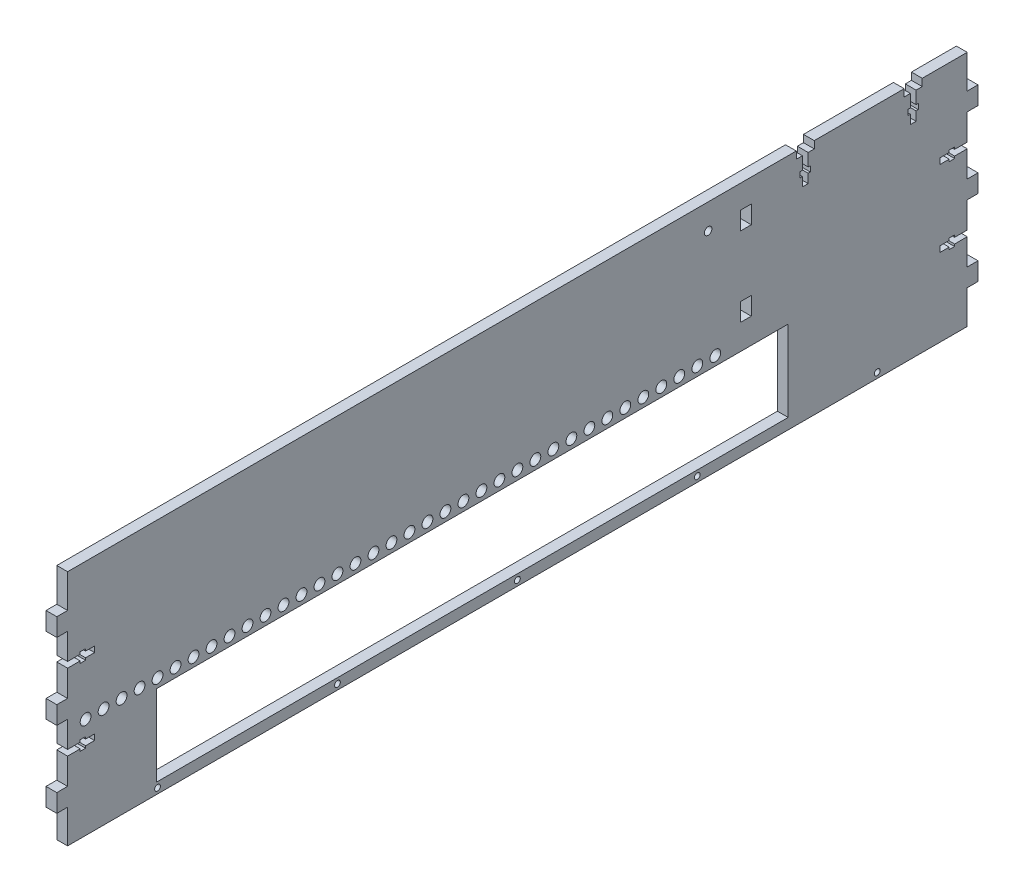
SolidWorks part; units mm, degrees
ref_plane "Front Plane" through (0, 0, 0) normal (0, 0, 1) x (1, 0, 0)
ref_plane "Top Plane" through (0, 0, 0) normal (0, 1, 0) x (1, 0, 0)
ref_plane "Right Plane" through (0, 0, 0) normal (1, 0, 0) x (0, 0, -1)
sketch "Sketch1" plane through (0, 0, 0) normal (1, 0, 0) x (0, 0, -1)
  line L1 (-250, -66) -> (250, -66)
  line L2 (-250, -66) -> (-250, 66)
  line L3 (-250, 66) -> (250, 66)
  line L4 (250, -66) -> (250, 66)
  line L5 (-250, -66) -> (250, 66) construction
  line L6 (-250, 66) -> (250, -66) construction
  point P0 (0, 0)
  dimension "D1" = 132
  dimension "D2" = 500
extrude "Boss-Extrude1" add sketch "Sketch1" along normal blind 6
sketch "Sketch4" plane through (0, 0, 250) normal (0, 0, 1) x (1, 0, 0)
  line L0 (0, 66) -> (0, -66) construction
  line L1 (0, 47.3321) -> (6, 47.3321)
  line L2 (0, 47.3321) -> (0, 37.3321)
  line L3 (0, 37.3321) -> (6, 37.3321)
  line L4 (6, 47.3321) -> (6, 37.3321)
  line L5 (6, 66) -> (6, -66) construction
  line L6 (0, 37.3321) -> (6, 37.3321) construction
  line L7 (0, -66) -> (0, 66) construction
  line L8 (6, 47.3321) -> (0, 47.3321) construction
  line L9 (0, -5) -> (6, -5) construction
  line L10 (0, -5) -> (6, -5)
  line L11 (0, -5) -> (0, 5)
  line L12 (0, 5) -> (6, 5)
  line L13 (6, -5) -> (6, 5)
  line L14 (6, -66) -> (6, 66) construction
  line L15 (6, 5) -> (0, 5) construction
  line L16 (6, -37.3321) -> (0, -37.3321) construction
  line L17 (0, -47.3321) -> (6, -47.3321)
  line L18 (0, -47.3321) -> (0, -37.3321)
  line L19 (0, -37.3321) -> (6, -37.3321)
  line L20 (6, -47.3321) -> (6, -37.3321)
  line L21 (0, -47.3321) -> (6, -47.3321) construction
extrude "Boss-Extrude2" add sketch "Sketch4" along normal blind 6
sketch "Sketch5" plane through (0, 0, 0) normal (-1, 0, 0) x (0, 0, 1)
  line L0 (250, 37.3321) -> (250, 5) construction
  line L1 (250, 5) -> (250, -5) construction
  line L2 (250, -5) -> (250, -37.3321) construction
  line L3 (250, 21.1661) -> (235, 21.1661) construction
  line L4 (240, -23.9661) -> (243, -18.3661) construction
  line L5 (250, 22.7661) -> (235, 22.7661)
  line L6 (240, -18.3661) -> (243, -23.9661) construction
  line L7 (250, 19.5661) -> (235, 19.5661)
  line L8 (250, -21.1661) -> (235, -21.1661) construction
  line L9 (250, 22.7661) -> (250, 19.5661)
  line L10 (235, 22.7661) -> (235, 19.5661)
  line L11 (243, -18.3661) -> (243, -23.9661)
  line L12 (240, -23.9661) -> (243, -23.9661)
  line L13 (250, 0) -> (222.8268, 0) construction
  line L14 (240, 18.3661) -> (243, 18.3661)
  line L15 (240, 18.3661) -> (240, 23.9661)
  line L16 (240, 23.9661) -> (243, 23.9661)
  line L17 (243, 18.3661) -> (243, 23.9661)
  line L18 (240, 18.3661) -> (243, 23.9661) construction
  line L19 (240, 23.9661) -> (243, 18.3661) construction
  line L20 (240, -18.3661) -> (240, -23.9661)
  line L21 (240, -18.3661) -> (243, -18.3661)
  line L22 (235, -22.7661) -> (235, -19.5661)
  line L23 (250, -22.7661) -> (250, -19.5661)
  line L24 (250, -19.5661) -> (235, -19.5661)
  line L25 (250, -22.7661) -> (235, -22.7661)
  point P20 (241.5, 21.1661)
  point P29 (241.5, -21.1661)
  dimension "D3" = 15
  dimension "D4" = 7
  dimension "D5" = 3
  dimension "D6" = 5.6
  dimension "D1" = 1.6
  dimension "D2" = 1.6
extrude "Cut-Extrude3" cut sketch "Sketch5" against normal up to next contours L17 L7 L9 L5 | L7 L17 L5 L15 | L5 L17 L16 L15 | L14 L17 L7 L15 | L7 L15 L5 L10 | L25 L23 L24 L11 | L25 L11 L24 L20 | L24 L11 L21 L20 | L11 L25 L20 L12 | L25 L20 L24 L22 region at (0, 21.1661, 246.5) region at (0, 21.1661, 241.5) region at (0, 23.3661, 241.5) region at (0, 21.1661, 237.5) region at (0, 18.9661, 241.5) region at (0, -18.9661, 241.5) region at (0, -21.1661, 246.5) region at (0, -21.1661, 241.5) region at (0, -23.3661, 241.5) region at (0, -21.1661, 237.5)
sketch "Sketch6" plane through (0, 0, -250) normal (0, 0, -1) x (-1, 0, 0)
  line L0 (0, 47.3321) -> (0, 37.3321) construction
  line L1 (0, 37.3321) -> (-6, 37.3321) construction
  line L2 (-6, 37.3321) -> (-6, 47.3321) construction
  line L3 (-6, 47.3321) -> (0, 47.3321) construction
  line L4 (0, 5) -> (0, -5) construction
  line L5 (0, -5) -> (-6, -5) construction
  line L6 (-6, -5) -> (-6, 5) construction
  line L7 (-6, 5) -> (0, 5) construction
  line L8 (0, -37.3321) -> (0, -47.3321) construction
  line L9 (0, -47.3321) -> (-6, -47.3321) construction
  line L10 (-6, -47.3321) -> (-6, -37.3321) construction
  line L11 (-6, -37.3321) -> (0, -37.3321) construction
  line L12 (0, 47.3321) -> (0, 37.3321)
  line L13 (0, 37.3321) -> (-6, 37.3321)
  line L14 (-6, 37.3321) -> (-6, 47.3321)
  line L15 (-6, 47.3321) -> (0, 47.3321)
  line L16 (0, 5) -> (0, -5)
  line L17 (0, -5) -> (-6, -5)
  line L18 (-6, -5) -> (-6, 5)
  line L19 (-6, 5) -> (0, 5)
  line L20 (0, -37.3321) -> (0, -47.3321)
  line L21 (0, -47.3321) -> (-6, -47.3321)
  line L22 (-6, -47.3321) -> (-6, -37.3321)
  line L23 (-6, -37.3321) -> (0, -37.3321)
extrude "Boss-Extrude3" add sketch "Sketch6" along normal blind 6
sketch "Sketch7" plane through (0, 0, 0) normal (-1, 0, 0) x (0, 0, 1)
  line L0 (0, 0) -> (0, -63.2146) construction
  line L1 (240, 22.7661) -> (240, 23.9661) construction
  line L2 (240, 22.7661) -> (235, 22.7661) construction
  line L3 (235, 22.7661) -> (235, 19.5661) construction
  line L4 (240, 19.5661) -> (235, 19.5661) construction
  line L5 (240, 18.3661) -> (240, 19.5661) construction
  line L6 (240, 18.3661) -> (243, 18.3661) construction
  line L7 (243, 18.3661) -> (243, 19.5661) construction
  line L8 (250, 19.5661) -> (243, 19.5661) construction
  line L9 (250, 22.7661) -> (243, 22.7661) construction
  line L10 (240, 23.9661) -> (243, 23.9661) construction
  line L11 (243, 22.7661) -> (243, 23.9661) construction
  line L12 (240, 22.7661) -> (235, 22.7661) construction
  line L13 (235, 22.7661) -> (235, 19.5661) construction
  line L14 (240, 19.5661) -> (235, 19.5661) construction
  line L15 (240, 18.3661) -> (240, 19.5661) construction
  line L16 (240, 18.3661) -> (243, 18.3661) construction
  line L17 (243, 18.3661) -> (243, 19.5661) construction
  line L18 (250, 19.5661) -> (243, 19.5661) construction
  line L19 (250, 22.7661) -> (243, 22.7661) construction
  line L20 (240, 23.9661) -> (243, 23.9661) construction
  line L21 (243, 22.7661) -> (243, 23.9661) construction
  line L22 (240, 22.7661) -> (240, 23.9661) construction
  line L23 (250, -19.5661) -> (243, -19.5661) construction
  line L24 (240, -18.3661) -> (243, -18.3661) construction
  line L25 (243, -18.3661) -> (243, -19.5661) construction
  line L26 (240, -18.3661) -> (240, -19.5661) construction
  line L27 (240, -19.5661) -> (235, -19.5661) construction
  line L28 (235, -22.7661) -> (235, -19.5661) construction
  line L29 (240, -22.7661) -> (235, -22.7661) construction
  line L30 (240, -22.7661) -> (240, -23.9661) construction
  line L31 (240, -23.9661) -> (243, -23.9661) construction
  line L32 (243, -22.7661) -> (243, -23.9661) construction
  line L33 (250, -22.7661) -> (243, -22.7661) construction
  line L34 (250, -19.5661) -> (243, -19.5661) construction
  line L35 (240, -18.3661) -> (243, -18.3661) construction
  line L36 (243, -18.3661) -> (243, -19.5661) construction
  line L37 (240, -18.3661) -> (240, -19.5661) construction
  line L38 (240, -19.5661) -> (235, -19.5661) construction
  line L39 (235, -22.7661) -> (235, -19.5661) construction
  line L40 (240, -22.7661) -> (235, -22.7661) construction
  line L41 (240, -22.7661) -> (240, -23.9661) construction
  line L42 (240, -23.9661) -> (243, -23.9661) construction
  line L43 (243, -22.7661) -> (243, -23.9661) construction
  line L44 (250, -22.7661) -> (243, -22.7661) construction
  line L45 (250, 22.7661) -> (250, 19.5661) construction
  line L46 (250, -19.5661) -> (250, -22.7661) construction
  line L47 (-250, -19.5661) -> (-250, -22.7661)
  line L48 (-250, 22.7661) -> (-250, 19.5661)
  line L49 (-250, -22.7661) -> (-243, -22.7661)
  line L50 (-243, -22.7661) -> (-243, -23.9661)
  line L51 (-240, -23.9661) -> (-243, -23.9661)
  line L52 (-240, -22.7661) -> (-240, -23.9661)
  line L53 (-240, -22.7661) -> (-235, -22.7661)
  line L54 (-235, -22.7661) -> (-235, -19.5661)
  line L55 (-240, -19.5661) -> (-235, -19.5661)
  line L56 (-240, -18.3661) -> (-240, -19.5661)
  line L57 (-243, -18.3661) -> (-243, -19.5661)
  line L58 (-240, -18.3661) -> (-243, -18.3661)
  line L59 (-250, -19.5661) -> (-243, -19.5661)
  line L60 (-240, 22.7661) -> (-240, 23.9661)
  line L61 (-243, 22.7661) -> (-243, 23.9661)
  line L62 (-240, 23.9661) -> (-243, 23.9661)
  line L63 (-250, 22.7661) -> (-243, 22.7661)
  line L64 (-250, 19.5661) -> (-243, 19.5661)
  line L65 (-243, 18.3661) -> (-243, 19.5661)
  line L66 (-240, 18.3661) -> (-243, 18.3661)
  line L67 (-240, 18.3661) -> (-240, 19.5661)
  line L68 (-240, 19.5661) -> (-235, 19.5661)
  line L69 (-235, 22.7661) -> (-235, 19.5661)
  line L70 (-240, 22.7661) -> (-235, 22.7661)
extrude "Cut-Extrude4" cut sketch "Sketch7" against normal up to next
sketch "Sketch8" plane through (0, 0, 0) normal (-1, 0, 0) x (0, 0, 1)
  line L0 (200, -15.55) -> (-150, -15.55) construction
  line L1 (200, -15.55) -> (-150, -15.55) construction
  line L2 (200, -15.55) -> (200, -60) construction
  line L3 (200, -15.55) -> (200, -60) construction
  line L186 (-150, -15.55) -> (-150, -60) construction
  line L187 (-150, -60) -> (200, -60) construction
  line L188 (200.5, -15.05) -> (200.5, -60)
  line L189 (200.5, -15.05) -> (-150.5, -15.05)
  line L190 (-150.5, -15.05) -> (-150.5, -60)
  line L191 (-150.5, -60) -> (200.5, -60)
  dimension "D1" = 0.5
extrude "Cut-Extrude5" cut sketch "Sketch8" against normal up to next
sketch "Sketch10" plane through (6, 0, 0) normal (1, 0, 0) x (0, 0, -1)
  line L0 (0, 0) -> (0, -66) construction
  line L1 (-250, -66) -> (250, -66) construction
  line L2 (0, -63) -> (250, -63) construction
  line L3 (250, -66) -> (250, -47.3321) construction
  circle A0 centre (0, -63) radius 1.6
  circle A1 centre (100, -63) radius 1.6
  circle A2 centre (200, -63) radius 1.6
  circle A3 centre (-100, -63) radius 1.6
  circle A4 centre (-200, -63) radius 1.6
  dimension "D2" = 3.2
  dimension "D1" = 3
  dimension "D3" = 100
  dimension "D4" = 100
extrude "Cut-Extrude7" cut sketch "Sketch10" against normal up to next
sketch "Sketch11" plane through (6, 0, 0) normal (1, 0, 0) x (0, 0, -1)
  line L0 (130, 43) -> (130, 53) construction
  line L1 (130, 53) -> (124, 53) construction
  line L2 (124, 53) -> (124, 43) construction
  line L3 (124, 43) -> (130, 43) construction
  line L4 (130, -1) -> (130, 9) construction
  line L5 (130, 9) -> (124, 9) construction
  line L6 (124, 9) -> (124, -1) construction
  line L7 (124, -1) -> (130, -1) construction
  line L8 (130, 43) -> (130, 53)
  line L9 (130, 53) -> (124, 53)
  line L10 (124, 53) -> (124, 43)
  line L11 (124, 43) -> (130, 43)
  line L12 (130, -1) -> (130, 9)
  line L13 (130, 9) -> (124, 9)
  line L14 (124, 9) -> (124, -1)
  line L15 (124, -1) -> (130, -1)
extrude "Cut-Extrude8" cut sketch "Sketch11" against normal up to next
sketch "Sketch12" plane through (0, 0, 0) normal (-1, 0, 0) x (0, 0, 1)
  line L0 (-124, 53) -> (-124, 43) construction
  line L1 (-250, 66) -> (250, 66) construction
  circle A0 centre (-106, 52) radius 2.1
  dimension "D1" = 18
  dimension "D3" = 4.2
  dimension "D2" = 14
extrude "Cut-Extrude9" cut sketch "Sketch12" against normal up to next
sketch "Sketch13" plane through (0, 66, 0) normal (0, 1, 0) x (1, 0, 0)
  line L0 (6, 250) -> (6, -250) construction
  line L1 (0, 215) -> (6, 215)
  line L2 (0, 215) -> (0, 225)
  line L3 (0, 225) -> (6, 225)
  line L4 (6, 215) -> (6, 225)
  line L5 (0, 215) -> (6, 225) construction
  line L6 (0, 225) -> (6, 215) construction
  line L7 (6, 225) -> (0, 225) construction
  line L8 (6, 165) -> (0, 165) construction
  line L9 (0, 155) -> (6, 155)
  line L10 (0, 155) -> (0, 165)
  line L11 (0, 165) -> (6, 165)
  line L12 (6, 155) -> (6, 165)
  line L13 (0, 155) -> (6, 165) construction
  line L14 (0, 165) -> (6, 155) construction
  point P0 (3, 220)
  point P10 (3, 160)
extrude "Cut-Extrude10" cut sketch "Sketch13" against normal blind 4
sketch "Sketch14" plane through (0, 0, 0) normal (-1, 0, 0) x (0, 0, 1)
  circle A0 centre (240, -10) radius 3 construction
  circle A1 centre (240, -10) radius 3
  circle A2 centre (230, -10) radius 3
  circle A3 centre (220, -10) radius 3
  circle A4 centre (210, -10) radius 3
  circle A5 centre (200, -10) radius 3
  circle A6 centre (190, -10) radius 3
  circle A7 centre (180, -10) radius 3
  circle A8 centre (170, -10) radius 3
  circle A9 centre (160, -10) radius 3
  circle A10 centre (150, -10) radius 3
  circle A11 centre (140, -10) radius 3
  circle A12 centre (130, -10) radius 3
  circle A13 centre (120, -10) radius 3
  circle A14 centre (110, -10) radius 3
  circle A15 centre (100, -10) radius 3
  circle A16 centre (90, -10) radius 3
  circle A17 centre (80, -10) radius 3
  circle A18 centre (70, -10) radius 3
  circle A19 centre (60, -10) radius 3
  circle A20 centre (50, -10) radius 3
  circle A21 centre (40, -10) radius 3
  circle A22 centre (30, -10) radius 3
  circle A23 centre (20, -10) radius 3
  circle A24 centre (10, -10) radius 3
  circle A25 centre (0, -10) radius 3
  circle A26 centre (-10, -10) radius 3
  circle A27 centre (-20, -10) radius 3
  circle A28 centre (-30, -10) radius 3
  circle A29 centre (-40, -10) radius 3
  circle A30 centre (-50, -10) radius 3
  circle A31 centre (-60, -10) radius 3
  circle A32 centre (-70, -10) radius 3
  circle A33 centre (-80, -10) radius 3
  circle A34 centre (-90, -10) radius 3
  circle A35 centre (-100, -10) radius 3
  circle A36 centre (-110, -10) radius 3
  dimension "D1" = 36
extrude "Cut-Extrude11" cut sketch "Sketch14" against normal up to next (6 mm away)
sketch "Sketch15" plane through (6, 0, 0) normal (1, 0, 0) x (0, 0, -1)
  line L0 (160, 62) -> (160, 47) construction
  line L1 (155, 62) -> (165, 62) construction
  line L2 (220, 62) -> (220, 47) construction
  line L3 (215, 62) -> (225, 62) construction
  line L4 (160, 47) -> (220, 47) construction
  line L5 (190, 47) -> (190, 66) construction
  line L6 (215, 66) -> (165, 66) construction
  line L7 (158.4, 62) -> (158.4, 55)
  line L8 (161.6, 62) -> (161.6, 55)
  line L9 (158.4, 62) -> (161.6, 62)
  line L10 (158.4, 47) -> (161.6, 47)
  line L11 (161.6, 52) -> (162.8, 52)
  line L12 (157.2, 55) -> (158.4, 55)
  line L13 (157.2, 55) -> (157.2, 52)
  line L14 (157.2, 52) -> (158.4, 52)
  line L15 (162.8, 55) -> (162.8, 52)
  line L16 (157.2, 55) -> (162.8, 52) construction
  line L17 (157.2, 52) -> (162.8, 55) construction
  line L18 (161.6, 55) -> (162.8, 55)
  line L19 (158.4, 52) -> (158.4, 47)
  line L20 (158.4, 62) -> (158.4, 47) construction
  line L21 (161.6, 52) -> (161.6, 47)
  line L22 (161.6, 62) -> (161.6, 47) construction
  line L23 (222.8, 52) -> (217.2, 55) construction
  line L24 (222.8, 55) -> (217.2, 52) construction
  line L25 (220, 62) -> (220, 47) construction
  line L26 (218.4, 52) -> (218.4, 47)
  line L27 (221.6, 52) -> (221.6, 47)
  line L28 (218.4, 55) -> (217.2, 55)
  line L29 (217.2, 55) -> (217.2, 52)
  line L30 (222.8, 52) -> (221.6, 52)
  line L31 (222.8, 55) -> (222.8, 52)
  line L32 (222.8, 55) -> (221.6, 55)
  line L33 (218.4, 52) -> (217.2, 52)
  line L34 (221.6, 47) -> (218.4, 47)
  line L35 (221.6, 62) -> (218.4, 62)
  line L36 (218.4, 62) -> (218.4, 55)
  line L37 (221.6, 62) -> (221.6, 55)
  point P16 (160, 53.5)
  point P37 (220, 53.5)
  dimension "D3" = 15
  dimension "D4" = 7
  dimension "D5" = 3
  dimension "D6" = 5.6
  dimension "D1" = 1.6
  dimension "D2" = 1.6
extrude "Cut-Extrude12" cut sketch "Sketch15" against normal up to next
